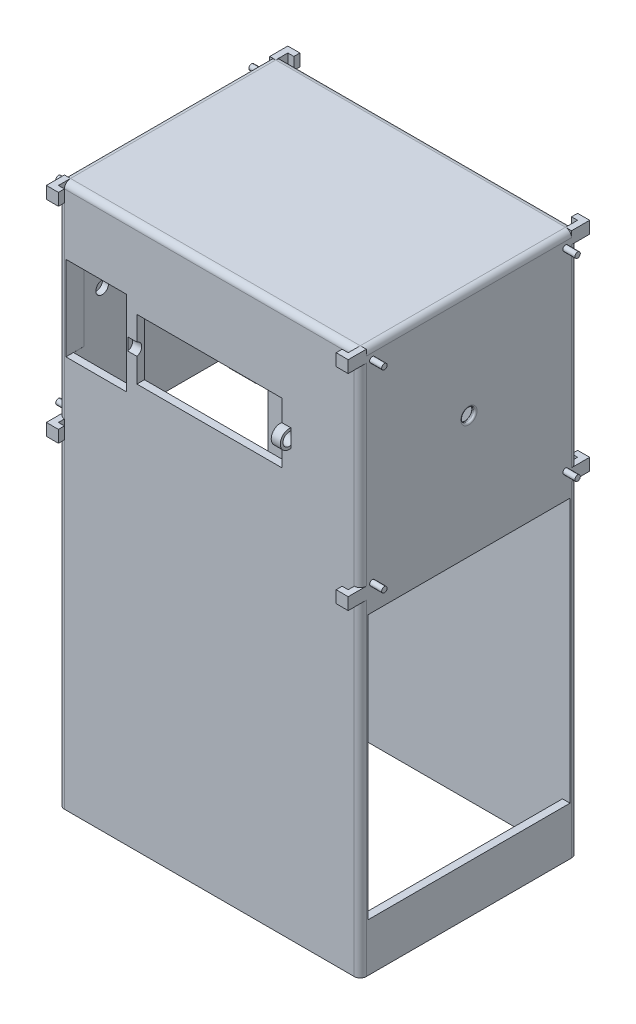
SolidWorks part; units mm, degrees
ref_plane "Front Plane" through (0, 0, 0) normal (0, 0, 1) x (1, 0, 0)
ref_plane "Top Plane" through (0, 0, 0) normal (0, 1, 0) x (1, 0, 0)
ref_plane "Right Plane" through (0, 0, 0) normal (1, 0, 0) x (0, 0, -1)
sketch "Sketch1" plane through (0, 0, 0) normal (0, 1, 0) x (1, 0, 0)
  line L1 (-63.5, -45.72) -> (63.5, -45.72)
  line L2 (-63.5, -45.72) -> (-63.5, 45.72)
  line L3 (-63.5, 45.72) -> (63.5, 45.72)
  line L4 (63.5, -45.72) -> (63.5, 45.72)
  line L5 (-63.5, -45.72) -> (63.5, 45.72) construction
  line L6 (-63.5, 45.72) -> (63.5, -45.72) construction
  point P0 (0, 0)
  dimension "D1" = 91.44
  dimension "D2" = 127
extrude "Boss-Extrude1" add sketch "Sketch1" along normal blind 228.6
sketch "Sketch2" plane through (63.5, 0, 0) normal (1, 0, 0) x (0, 0, -1)
  line L1 (-45.72, 137.16) -> (45.72, 137.16) construction
  line L2 (-45.72, 137.16) -> (-45.72, 228.6) construction
  line L3 (-45.72, 228.6) -> (45.72, 228.6) construction
  line L4 (45.72, 137.16) -> (45.72, 228.6) construction
  line L5 (-45.72, 137.16) -> (45.72, 228.6) construction
  line L6 (-45.72, 228.6) -> (45.72, 137.16) construction
  circle A0 centre (0, 182.88) radius 2.667
  point P0 (0, 182.88)
  dimension "D2" = 5.334
  dimension "D1" = 91.44
sketch "Sketch3" plane through (0, 0, 0) normal (0, -1, 0) x (1, 0, 0)
  line L0 (63.5, 45.72) -> (63.5, -45.72) construction
  line L1 (-60.325, -42.545) -> (60.325, -42.545)
  line L2 (-60.325, -42.545) -> (-60.325, 42.545)
  line L3 (-60.325, 42.545) -> (60.325, 42.545)
  line L4 (60.325, -42.545) -> (60.325, 42.545)
  line L5 (-60.325, -42.545) -> (60.325, 42.545) construction
  line L6 (-60.325, 42.545) -> (60.325, -42.545) construction
  line L7 (-63.5, 45.72) -> (63.5, 45.72) construction
  point P0 (0, 0)
  dimension "D1" = 3.175
  dimension "D2" = 3.175
extrude "Cut-Extrude1" cut sketch "Sketch3" against normal blind 226.06
extrude "Cut-Extrude2" cut sketch "Sketch2" against normal through all contours A0
sketch "Sketch4" plane through (63.5, 0, 0) normal (1, 0, 0) x (0, 0, -1)
  line L3 (-45.72, 228.6) -> (45.72, 228.6) construction
  circle A0 centre (-40.64, 223.52) radius 1.143
  circle A1 centre (40.64, 223.52) radius 1.143
  circle A2 centre (40.64, 142.24) radius 1.143
  circle A3 centre (-40.64, 142.24) radius 1.143
  point P0 (0, 182.88)
  dimension "D7" = 2.286
extrude "Boss-Extrude3" add sketch "Sketch4" along normal blind 5.08
sketch "Sketch5" plane through (60.325, 0, 0) normal (-1, 0, 0) x (0, 0, 1)
  circle A0 centre (0, 182.88) radius 20.32
  dimension "D1" = 40.64
extrude "Cut-Extrude3" cut sketch "Sketch5" against normal blind 1.27
fillet "Fillet1" radius 0.762 1 edges at (61.595, 182.88, 2.667)
fillet "Fillet2" radius 0.762 1 edges at (63.5, 182.88, -2.667)
sketch "Sketch6" plane through (0, 0, 45.72) normal (0, 0, 1) x (1, 0, 0)
  line L0 (0, 0) -> (0, 228.6) construction
  line L1 (-63.5, 228.6) -> (63.5, 228.6) construction
  line L3 (2.7526, 228.6) -> (2.7526, 182.88) construction
  line L4 (-30.48, 170.18) -> (30.48, 170.18)
  line L5 (30.48, 170.18) -> (30.48, 195.58)
  line L6 (-30.48, 170.18) -> (-30.48, 195.58)
  line L7 (30.48, 195.58) -> (-30.48, 195.58)
  line L8 (-30.48, 182.88) -> (30.48, 182.88) construction
  point P10 (0, 170.18)
  dimension "D1" = 45.72
  dimension "D2" = 60.96
  dimension "D3" = 25.4
mirror "Mirror2" about plane through (0, 0, 0) normal (1, 0, 0) of "Cut-Extrude3", "Boss-Extrude3"
fillet "Fillet3" radius 0.762 2 edges at (-61.595, 182.88, -2.667) (-63.5, 182.88, -2.667)
extrude "Cut-Extrude4" cut sketch "Sketch6" against normal through all
fillet "Fillet4" radius 2.54 8 edges at (63.5, 228.6, 0) (0, 228.6, 45.72) (0, 228.6, -45.72) (-63.5, 228.6, 0) (-63.5, 114.3, -45.72) (-63.5, 114.3, 45.72) (63.5, 114.3, 45.72) (63.5, 114.3, -45.72)
sketch "Sketch7" plane through (63.5, 0, 0) normal (1, 0, 0) x (0, 0, -1)
  line L0 (45.72, 226.06) -> (45.72, 0) construction
  line L1 (-42.545, 20.32) -> (42.545, 20.32)
  line L2 (-42.545, 20.32) -> (-42.545, 131.4726)
  line L3 (-42.545, 131.4726) -> (42.545, 131.4726)
  line L4 (42.545, 20.32) -> (42.545, 131.4726)
  line L5 (-42.545, 20.32) -> (42.545, 131.4726) construction
  line L6 (-42.545, 131.4726) -> (42.545, 20.32) construction
  line L7 (-45.72, 0) -> (-45.72, 226.06) construction
  line L8 (-43.18, 0) -> (43.18, 0) construction
  point P0 (0, 75.8963)
  dimension "D1" = 3.175
  dimension "D2" = 3.175
  dimension "D3" = 20.32
extrude "Cut-Extrude5" cut sketch "Sketch7" against normal through all
sketch "Sketch10" plane through (60.325, 0, 0) normal (-1, 0, 0) x (0, 0, 1)
  line L0 (0, 182.88) -> (-30.48, 182.88) construction
  line L1 (-43.18, 226.06) -> (43.18, 226.06) construction
  circle A0 centre (-30.48, 182.88) radius 2.667
  dimension "D2" = 5.334
  dimension "D1" = 30.48
extrude "Cut-Extrude6" cut sketch "Sketch10" against normal blind 2.54
sketch "Sketch11" plane through (60.325, 0, 0) normal (-1, 0, 0) x (0, 0, 1)
  line L0 (-30.48, 182.88) -> (-45.72, 182.88) construction
  dimension "D1" = 15.24
sketch "Sketch12" plane through (0, 0, -45.72) normal (0, 0, -1) x (-1, 0, 0)
  line L1 (-34.8104, 182.8079) -> (-34.8104, 200.5879)
  line L2 (-34.8104, 182.8079) -> (-34.8104, 165.0279)
  line L3 (-34.8104, 165.0279) -> (-60.2104, 165.0279)
  line L4 (-60.2104, 165.0279) -> (-60.2104, 182.8079)
  line L5 (-34.8104, 200.5879) -> (-60.2104, 200.5879)
  line L6 (-60.2104, 200.5879) -> (-60.2104, 182.8079)
  dimension "D1" = 25.4
  dimension "D2" = 17.78
  dimension "D3" = 35.56
extrude "Cut-Extrude7" cut sketch "Sketch12" against normal blind 7.62
sketch "Sketch13" plane through (-60.325, 0, 0) normal (1, 0, 0) x (0, 0, -1)
  line L0 (0, 182.88) -> (-30.48, 182.88) construction
  circle A0 centre (-30.48, 182.88) radius 2.667
  dimension "D2" = 5.334
  dimension "D1" = 30.48
extrude "Cut-Extrude8" cut sketch "Sketch13" against normal blind 2.54
sketch "Sketch15" plane through (-60.325, 0, 0) normal (1, 0, 0) x (0, 0, -1)
  line L0 (-30.48, 182.88) -> (-45.72, 182.88) construction
  dimension "D1" = 15.24
sketch "Sketch16" plane through (0, 0, 45.72) normal (0, 0, 1) x (1, 0, 0)
  line L0 (-60.3464, 182.9342) -> (-60.3464, 200.7142)
  line L1 (-60.3464, 182.9342) -> (-60.3464, 165.1542)
  line L2 (-60.3464, 165.1542) -> (-34.9464, 165.1542)
  line L3 (-34.9464, 165.1542) -> (-34.9464, 200.7142)
  line L4 (-34.9464, 200.7142) -> (-60.3464, 200.7142)
  dimension "D1" = 17.78
  dimension "D2" = 17.78
  dimension "D3" = 25.4
extrude "Cut-Extrude9" cut sketch "Sketch16" against normal blind 7.62
sketch "Sketch17" plane through (-63.5, 0, 0) normal (-1, 0, 0) x (0, 0, 1)
sketch "Sketch20" plane through (0, 226.06, 0) normal (0, -1, 0) x (1, 0, 0)
  line L0 (62.865, -30.48) -> (-4.445, -30.48) construction
  line L1 (62.865, -27.813) -> (62.865, -33.147) construction
  line L2 (-4.445, -30.48) -> (6.985, -30.48) construction
  line L3 (6.985, -34.29) -> (6.985, -26.67)
  line L4 (6.985, -34.29) -> (-4.445, -34.29)
  line L5 (-4.445, -34.29) -> (-4.445, -26.67)
  line L6 (-4.445, -26.67) -> (6.985, -26.67)
  point P8 (6.985, -30.48)
  dimension "D1" = 67.31
  dimension "D2" = 11.43
  dimension "D3" = 7.62
extrude "Boss-Extrude4" add sketch "Sketch20" along normal blind 50.8
sketch "Sketch21" plane through (6.985, 0, 0) normal (1, 0, 0) x (0, 0, -1)
  circle A0 centre (30.48, 182.88) radius 2.667
  dimension "D1" = 5.334
extrude "Cut-Extrude10" cut sketch "Sketch21" against normal blind 12.7
sketch "Sketch23" plane through (6.985, 0, 0) normal (1, 0, 0) x (0, 0, -1)
  line L1 (27.813, 182.88) -> (26.67, 182.88)
  line L2 (26.67, 175.26) -> (26.67, 226.06) construction
  line L3 (26.67, 182.88) -> (26.67, 175.26)
  line L4 (26.67, 175.26) -> (34.29, 175.26)
  line L5 (34.29, 175.26) -> (34.29, 182.88)
  line L6 (34.29, 175.26) -> (34.29, 226.06) construction
  line L7 (34.29, 182.88) -> (27.813, 182.88)
  circle A0 centre (30.48, 182.88) radius 2.667 construction
extrude "Cut-Extrude11" cut sketch "Sketch23" against normal blind 12.7
sketch "Sketch24" plane through (30.48, 0, 0) normal (-1, 0, 0) x (0, 0, 1)
  line L0 (-30.48, 182.88) -> (-46.355, 182.88) construction
  circle A0 centre (-46.355, 182.88) radius 3.81
  dimension "D2" = 7.62
  dimension "D1" = 15.875
extrude "Boss-Extrude5" add sketch "Sketch24" against normal blind 3.81
sketch "Sketch25" plane through (30.48, 0, 0) normal (-1, 0, 0) x (0, 0, 1)
  circle A0 centre (-46.355, 182.88) radius 2.667
  dimension "D1" = 5.334
extrude "Cut-Extrude12" cut sketch "Sketch25" against normal blind 3.81
mirror "Mirror3" about plane through (0, 0, 0) normal (0, 0, 1) of "Boss-Extrude4", "Cut-Extrude10", "Cut-Extrude12", "Boss-Extrude5"
sketch "Sketch26" plane through (6.985, 0, 0) normal (1, 0, 0) x (0, 0, -1)
  line L0 (-27.813, 182.88) -> (-26.67, 182.88)
  line L1 (-26.67, 175.26) -> (-26.67, 226.06) construction
  line L2 (-26.67, 182.88) -> (-26.67, 175.26)
  line L3 (-26.67, 175.26) -> (-34.29, 175.26)
  line L4 (-34.29, 175.26) -> (-34.29, 182.88)
  line L5 (-30.48, 182.88) -> (-45.72, 182.88) construction
  line L6 (-34.29, 175.26) -> (-34.29, 226.06) construction
  line L7 (-34.29, 182.88) -> (-27.813, 182.88)
  circle A0 centre (-30.48, 182.88) radius 2.667 construction
extrude "Cut-Extrude13" cut sketch "Sketch26" against normal blind 12.7
sketch "Sketch27" plane through (30.48, 0, 0) normal (-1, 0, 0) x (0, 0, 1)
  circle A0 centre (-46.355, 182.88) radius 2.667
extrude "Cut-Extrude14" cut sketch "Sketch27" along normal blind 64.77 contours A0
sketch "Sketch29" plane through (30.48, 0, 0) normal (-1, 0, 0) x (0, 0, 1)
  circle A0 centre (46.355, 182.88) radius 2.667
extrude "Cut-Extrude15" cut sketch "Sketch29" along normal blind 64.77
sketch "Sketch31" plane through (0, 0, 0) normal (1, 0, 0) x (0, 0, -1)
  circle A0 centre (-46.355, 182.88) radius 12.7 construction
  dimension "D1" = 25.4
fillet "Fillet6" radius 50.8 1 edges at (1.27, 182.88, 34.29)
fillet "Fillet7" radius 50.8 1 edges at (1.27, 182.88, -34.29)
sketch "Sketch33" plane through (0, 228.6, 0) normal (0, 1, 0) x (1, 0, 0)
  line L0 (63.5, 43.18) -> (63.5, 50.8)
  line L1 (63.5, 50.8) -> (58.42, 50.8)
  line L2 (58.42, 50.8) -> (58.42, 48.26)
  line L3 (58.42, 48.26) -> (60.96, 48.26)
  line L4 (60.96, 48.26) -> (60.96, 43.18)
  line L5 (60.96, 43.18) -> (63.5, 43.18)
extrude "Boss-Extrude6" add sketch "Sketch33" against normal blind 5.08
mirror "Mirror4" about plane through (0, 0, 0) normal (1, 0, 0) of "Boss-Extrude6"
ref_plane "Plane1" through (0, 182.88, 0) normal (0, 1, 0) x (1, 0, 0)
mirror "Mirror5" about plane through (0, 182.88, 0) normal (0, 1, 0) of "Mirror4", "Boss-Extrude6"
mirror "Mirror6" about plane through (0, 0, 0) normal (0, 0, 1) of "Mirror5", "Boss-Extrude6", "Mirror4"
